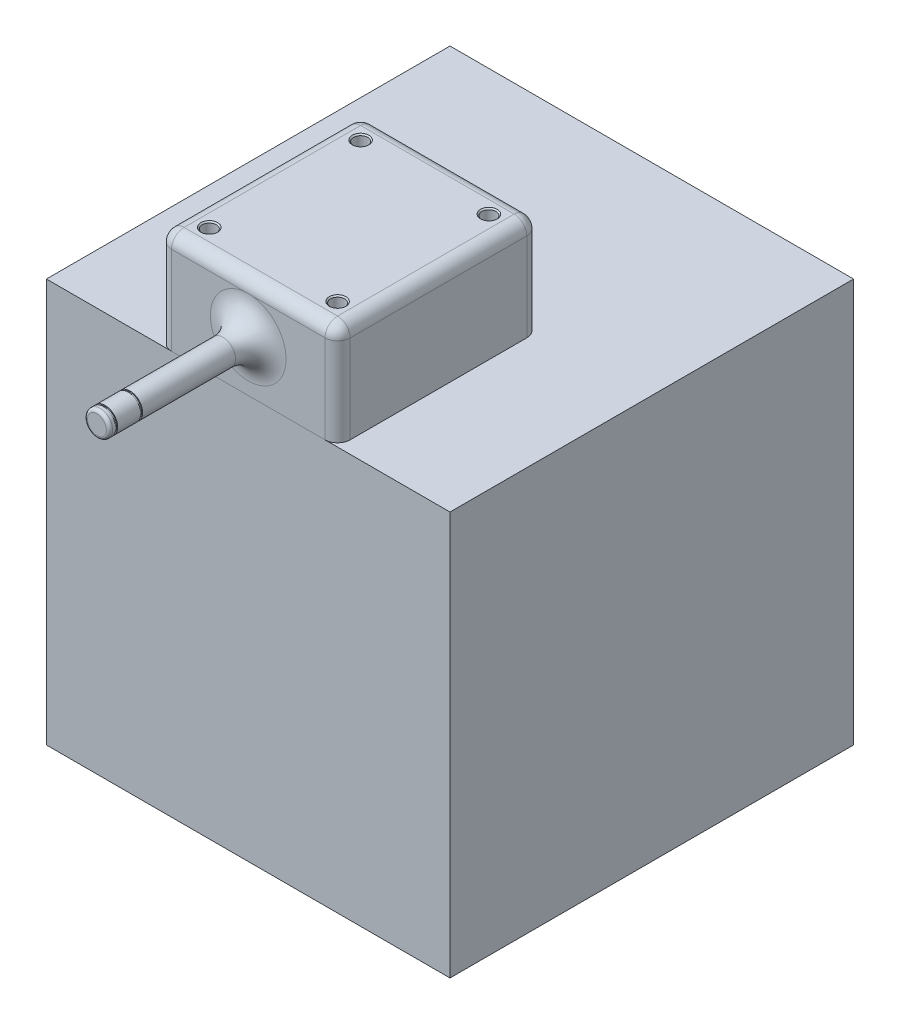
SolidWorks part; units mm, degrees
ref_plane "Front Plane" through (0, 0, 0) normal (0, 0, 1) x (1, 0, 0)
ref_plane "Top Plane" through (0, 0, 0) normal (0, 1, 0) x (1, 0, 0)
ref_plane "Right Plane" through (0, 0, 0) normal (1, 0, 0) x (0, 0, -1)
sketch "Sketch1" plane through (0, 0, 0) normal (0, 0, 1) x (1, 0, 0)
  line L1 (-45, 25.4) -> (45, 25.4)
  line L2 (-45, 25.4) -> (-45, -25.4)
  line L3 (-45, -25.4) -> (45, -25.4)
  line L4 (45, 25.4) -> (45, -25.4)
  line L5 (-45, 25.4) -> (45, -25.4) construction
  line L6 (-45, -25.4) -> (45, 25.4) construction
  circle A0 centre (0, 0) radius 6.35
  point P0 (0, 0)
  point P8 (22.9236, 12.0121)
  dimension "D1" = 12.7
  dimension "D2" = 90
  dimension "D3" = 50.8
extrude "Boss-Extrude1" add sketch "Sketch1" against normal blind 101.6 contours L2 L3 L4 L1
sketch "Sketch10" plane through (0, 0, 0) normal (0, 0, 1) x (1, 0, 0)
  line L0 (-45, -25.4) -> (45, -25.4) construction
  line L1 (-101.6, -25.4) -> (101.6, -25.4)
  line L2 (-101.6, -25.4) -> (-101.6, -228.6)
  line L3 (-101.6, -228.6) -> (101.6, -228.6)
  line L4 (101.6, -25.4) -> (101.6, -228.6)
  point P6 (0, -25.4)
  point P7 (0, -25.4)
  point P8 (143.1467, -25.4)
  point P9 (229.5126, -325.4)
  dimension "D1" = 203.2
extrude "Boss-Extrude3" add sketch "Sketch10" against normal blind 203.2 separate body
extrude "Boss-Extrude2" add sketch "Sketch1<3>" along normal blind 76.2 contours A0 region at (0, 0, 0)
sketch "Sketch1<3>" plane through (0, 0, 0) normal (0, 0, 1) x (1, 0, 0) same geometry as "Sketch1"
fillet "Fillet1" radius 6.35 8 edges at (45, 0, 0) (45, 0, -101.6) (-45, 0, -101.6) (-45, 0, 0) (0, 25.4, -101.6) (45, 25.4, -50.8) (0, 25.4, 0) (-45, 25.4, -50.8)
fillet "Fillet2" radius 12.7 1 edges at (6.35, 0, 0)
sketch "Sketch2" plane through (0, 25.4, 0) normal (0, 1, 0) x (1, 0, 0)
  line L0 (-38.65, 50.8) -> (0, 50.8) construction
  line L1 (-32.3, 88.9) -> (32.3, 88.9)
  line L2 (-32.3, 88.9) -> (-32.3, 12.7)
  line L3 (-32.3, 12.7) -> (32.3, 12.7)
  line L4 (32.3, 88.9) -> (32.3, 12.7)
  line L5 (-32.3, 88.9) -> (32.3, 12.7) construction
  line L6 (-32.3, 12.7) -> (32.3, 88.9) construction
  line L7 (-38.65, 95.25) -> (-38.65, 6.35) construction
  line L8 (0, 50.8) -> (0, 6.35) construction
  line L9 (-38.65, 6.35) -> (38.65, 6.35) construction
  line L10 (-32.3, 88.9) -> (-32.3, 95.25) construction
  line L11 (38.65, 95.25) -> (-38.65, 95.25) construction
  line L12 (-32.3, 88.9) -> (-38.65, 88.9) construction
  circle A0 centre (-32.3, 88.9) radius 3.175
  point P0 (0, 50.8)
  dimension "D1" = 6.35
  dimension "D2" = 3.175
hole_wizard "1/4 Clearance Hole1" positions "Sketch3" profile "Sketch4" hole size "1/4" standard "ANSI Inch" end condition through all
sketch "Sketch3" plane through (0, 25.4, 0) normal (0, 1, 0) x (1, 0, 0)
  point P0 (-32.3, 88.9)
  point P3 (-32.3, 12.7)
  point P6 (32.3, 12.7)
  point P9 (32.3, 88.9)
sketch "Sketch4" plane through (-32.3, 25.4, -88.9) normal (1, 0, 0) x (0, 0, 1)
  line L0 (0, 0) -> (0, 254)
  line L1 (0, 254) -> (3.5687, 254)
  line L2 (3.5687, 254) -> (3.5687, 0.635)
  line L3 (3.5687, 0.635) -> (4.2037, 0)
  line L5 (4.2037, 0) -> (0, 0)
  line L6 (-3.5687, 0.635) -> (-4.2037, 0) construction
  line L11 (0, -6.35) -> (0, 107.95) construction
  dimension "Thru Hole Dia." = 7.1374
  dimension "Thru Hole Depth" = 254
  dimension "Near C'Sink Dia." = 8.4074
  dimension "Near C'Sink Angle" = 90
ref_plane "Plane1" through (0, 6.35, 0) normal (0, 1, 0) x (1, 0, 0)
sketch "Sketch5" plane through (0, 6.35, 0) normal (0, 1, 0) x (1, 0, 0)
  line L0 (-45, -60.4625) -> (45, -60.4625)
  line L1 (-45, -72.0725) -> (45, -72.0725)
  line L2 (-45, -72.0725) -> (-45, -60.4625)
  line L3 (45, -60.4625) -> (45, -72.0725)
  line L4 (-45, -66.2675) -> (0, -66.2675) construction
  line L5 (0, -60.4625) -> (0, -72.0725) construction
  line L6 (0, -76.2) -> (0, -72.0725) construction
  line L7 (-6.35, -76.2) -> (6.35, -76.2) construction
  line L8 (-6.6675, -73.025) -> (0, -72.0725) construction
  line L9 (-6.6675, -72.0725) -> (6.6675, -72.0725)
  line L10 (-6.6675, -72.0725) -> (-6.6675, -73.025)
  line L11 (-6.6675, -73.025) -> (6.6675, -73.025)
  line L12 (6.6675, -72.0725) -> (6.6675, -73.025)
  line L13 (0, -72.0725) -> (6.6675, -73.025) construction
  line L14 (0, -60.4625) -> (6.6675, -59.51) construction
  line L15 (-6.6675, -59.51) -> (0, -60.4625) construction
  line L16 (6.6675, -60.4625) -> (6.6675, -59.51)
  line L17 (-6.6675, -59.51) -> (6.6675, -59.51)
  line L18 (-6.6675, -60.4625) -> (-6.6675, -59.51)
  line L19 (-6.6675, -60.4625) -> (6.6675, -60.4625)
  point P14 (8.7429, -41.5552)
  point P15 (-6.6675, -41.2491)
  point P21 (6.6675, -40.9034)
  point P22 (0, 0)
  point P23 (0, 0)
  point P24 (0, 0)
  dimension "D1" = 11.61
  dimension "D2" = 90
  dimension "D3" = 0.9525
  dimension "D4" = 13.335
  dimension "D5" = 3.175
ref_plane "Plane2" through (0, 0, 72.0725) normal (0, 0, 1) x (1, 0, 0)
ref_plane "Plane3" through (0, 0, 60.4625) normal (0, 0, 1) x (1, 0, 0)
sketch "Sketch6" plane through (0, 0, 76.2) normal (0, 0, 1) x (1, 0, 0)
  circle A0 centre (0, 0) radius 5.842
  dimension "D1" = 11.684
sketch "Sketch7" plane through (0, 0, 72.0725) normal (0, 0, 1) x (1, 0, 0)
  circle A1 centre (0, 0) radius 5.842
  circle A2 centre (0, 0) radius 5.842
  circle A3 centre (0, 0) radius 6.35
  circle A4 centre (0, 0) radius 6.35
  dimension "D1" = 0
  dimension "D2" = 0
sketch "Sketch8" plane through (0, 0, 60.4625) normal (0, 0, 1) x (1, 0, 0)
  circle A1 centre (0, 0) radius 5.842
  circle A2 centre (0, 0) radius 5.842
  circle A3 centre (0, 0) radius 6.35
  circle A4 centre (0, 0) radius 6.35
  dimension "D1" = 0
  dimension "D2" = 0
extrude "Cut-Extrude1" cut sketch "Sketch7" along normal up to vertex (0.9525 mm away) contours A4 A2 region at (-6.1704, 0, 72.0725) up to point (6.6675, 6.35, 73.025)
extrude "Cut-Extrude2" cut sketch "Sketch8" against normal up to vertex (0.9525 mm away) contours A4 A2 region at (-6.1704, 0, 60.4625) up to point (-6.6675, 6.35, 59.51)
fillet "Fillet3" radius 1.5875 1 edges at (6.35, 0, 76.2)
